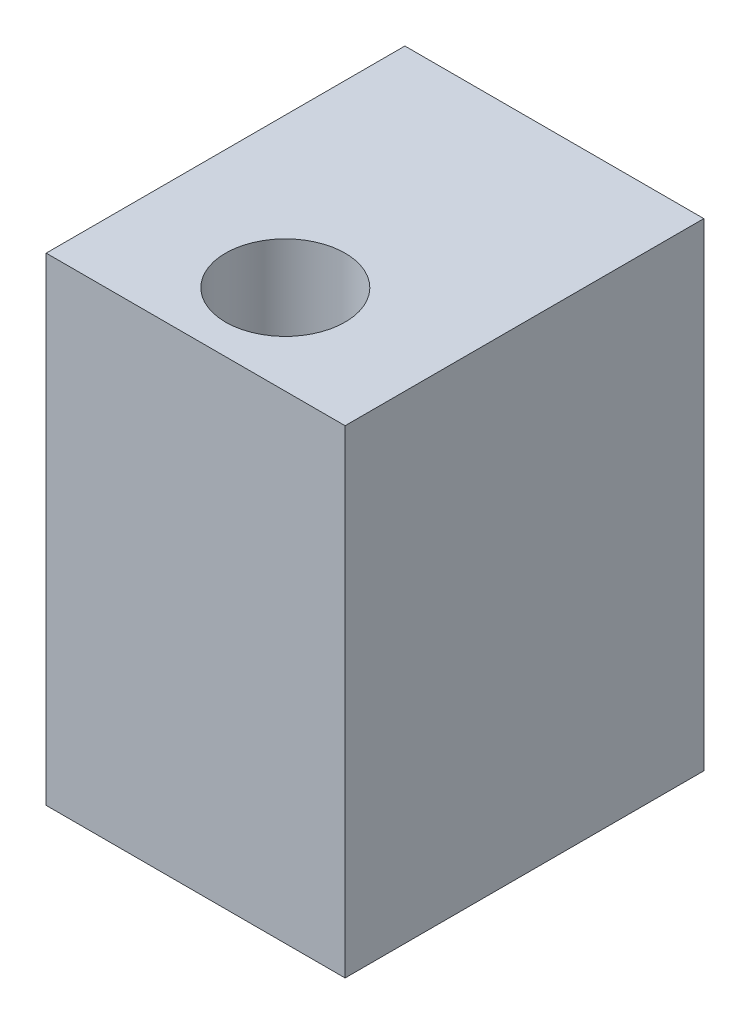
SolidWorks part; units mm, degrees
ref_plane "Front Plane" through (0, 0, 0) normal (0, 0, 1) x (1, 0, 0)
ref_plane "Top Plane" through (0, 0, 0) normal (0, 1, 0) x (1, 0, 0)
ref_plane "Right Plane" through (0, 0, 0) normal (1, 0, 0) x (0, 0, -1)
sketch "Sketch1" plane through (0, 0, 0) normal (0, 1, 0) x (1, 0, 0)
  line L1 (-5, -6) -> (5, -6)
  line L2 (-5, -6) -> (-5, 6)
  line L3 (-5, 6) -> (5, 6)
  line L4 (5, -6) -> (5, 6)
  line L5 (-5, -6) -> (5, 6) construction
  line L6 (-5, 6) -> (5, -6) construction
  circle A0 centre (0, 0) radius 1.5
  circle A1 centre (0, 0) radius 2
  point P0 (0, 0)
  dimension "D3" = 3
  dimension "D1" = 10
  dimension "D2" = 12
  dimension "D4" = 0.5
extrude "Boss-Extrude1" add sketch "Sketch1" along normal blind 16 contours L4 L3 L2 L1
sketch "Sketch2" plane through (0, 16, 0) normal (0, 1, 0) x (1, 0, 0)
  line L0 (-5, 0) -> (5, 0) construction
  line L1 (-5, -6) -> (-5, 6) construction
  line L2 (5, -6) -> (5, 6) construction
  line L3 (5, 0) -> (-5, -6) construction
  line L4 (-5, -6) -> (0, 0) construction
  line L5 (0, 0) -> (0, -6) construction
  line L6 (-5, -6) -> (5, -6) construction
  line L7 (0, -6) -> (5, -6) construction
  line L8 (5, -6) -> (-5, 0) construction
  circle A0 centre (0, -3) radius 1.5
  circle A1 centre (0, -3) radius 2
  dimension "D1" = 3
  dimension "D2" = 0.5
extrude "Cut-Extrude1" cut sketch "Sketch2" against normal blind 16 contours A0
extrude "Cut-Extrude2" cut sketch "Sketch2<3>" against normal blind 8 contours A1
sketch "Sketch2<3>" plane through (0, 16, 0) normal (0, 1, 0) x (1, 0, 0) same geometry as "Sketch2"
